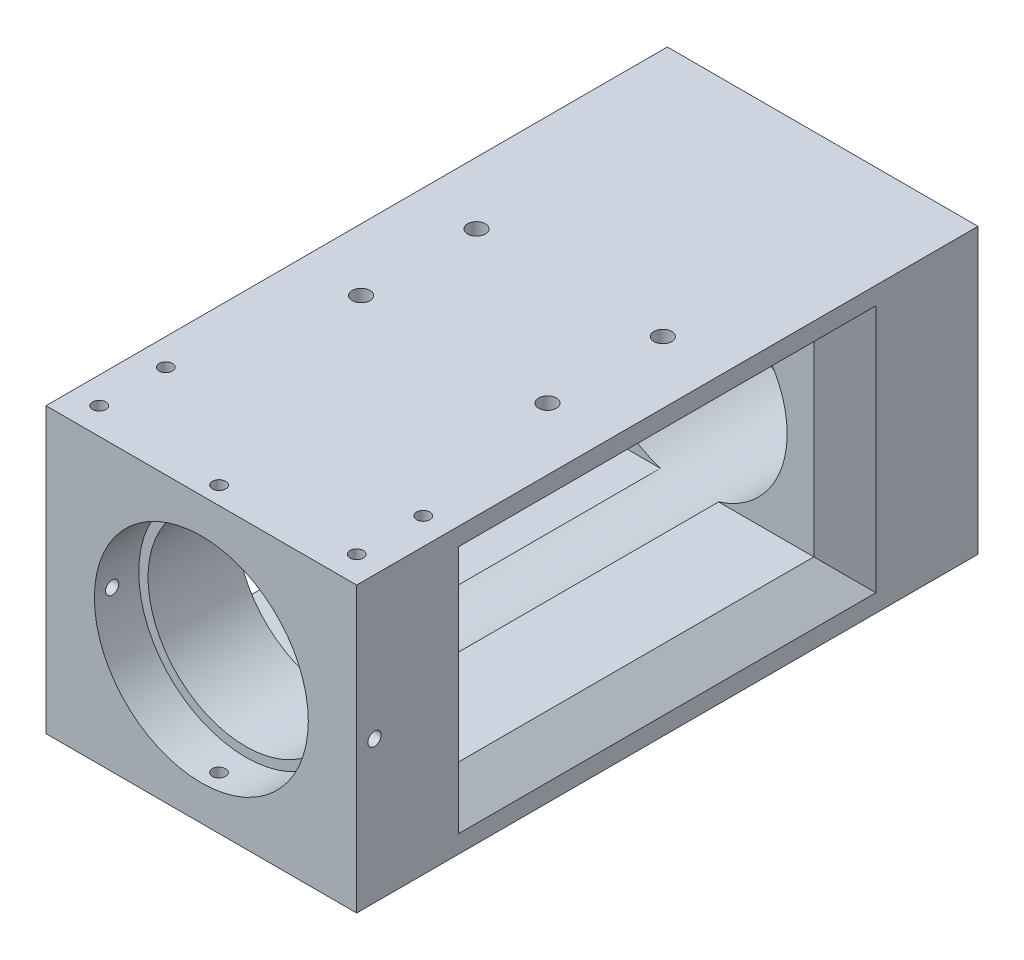
SolidWorks part; units mm, degrees
ref_plane "前视基准面" through (0, 0, 0) normal (0, 0, 1) x (1, 0, 0)
ref_plane "上视基准面" through (0, 0, 0) normal (0, 1, 0) x (1, 0, 0)
ref_plane "右视基准面" through (0, 0, 0) normal (1, 0, 0) x (0, 0, -1)
sketch "草图1" plane through (0, 0, 0) normal (0, 0, 1) x (1, 0, 0)
  line L1 (-35, -32) -> (35, -32)
  line L2 (-35, -32) -> (-35, 32)
  line L3 (-35, 32) -> (35, 32)
  line L4 (35, -32) -> (35, 32)
  line L5 (-35, -32) -> (35, 32) construction
  line L6 (-35, 32) -> (35, -32) construction
  point P0 (0, 0)
  dimension "D1" = 70
  dimension "D2" = 64
extrude "凸台-拉伸1" add sketch "草图1" along normal mid plane 140
sketch "草图2" plane through (0, 0, 70) normal (0, 0, 1) x (1, 0, 0)
  circle A0 centre (0, 0) radius 24.1
  dimension "D1" = 48.2
extrude "切除-拉伸1" cut sketch "草图2" against normal blind 10
sketch "草图3" plane through (0, 32, 0) normal (0, 1, 0) x (1, 0, 0)
  line L0 (35, -70) -> (-35, -70) construction
  circle A0 centre (0, -66) radius 1.5
  point P5 (0, -70)
  dimension "D1" = 3
  dimension "D2" = 4
extrude "切除-拉伸2" cut sketch "草图3" against normal through all
sketch "草图4" plane through (35, 0, 0) normal (1, 0, 0) x (0, 0, -1)
  line L0 (-70, -32) -> (-70, 32) construction
  circle A0 centre (-66, 0) radius 1.5
  dimension "D1" = 3
  dimension "D2" = 4
extrude "切除-拉伸3" cut sketch "草图4" against normal through all
sketch "草图5" plane through (0, 0, 60) normal (0, 0, 1) x (1, 0, 0)
  circle A0 centre (0, 0) radius 22
  dimension "D1" = 44
extrude "切除-拉伸4" cut sketch "草图5" against normal through all
sketch "草图6" plane through (35, 0, 0) normal (1, 0, 0) x (0, 0, -1)
  line L1 (-40, -21) -> (40, -21)
  line L2 (-40, -21) -> (-40, 21)
  line L3 (-40, 21) -> (40, 21)
  line L4 (40, -21) -> (40, 21)
  line L5 (-40, -21) -> (40, 21) construction
  line L6 (-40, 21) -> (40, -21) construction
  point P0 (0, 0)
  dimension "D1" = 42
  dimension "D2" = 80
extrude "切除-拉伸5" cut sketch "草图6" against normal through all
chamfer "倒角1" distance 7 angle 45 8 edges at (-35, 0, -40) (-35, -21, 0) (-35, 0, 40) (-35, 21, 0) (35, 21, 0) (35, 0, -40) (35, 0, 40) (35, -21, 0)
sketch "草图7" plane through (0, 32, 0) normal (0, 1, 0) x (1, 0, 0)
  line L0 (-21, 13) -> (21, 13) construction
  circle A0 centre (-21, 13) radius 2
  circle A1 centre (21, 13) radius 2
  point P4 (0, 13)
  dimension "D1" = 4
  dimension "D2" = 42
  dimension "D3" = 13
extrude "切除-拉伸6" cut sketch "草图7" against normal blind 20
sketch "草图8" plane through (0, 21, 0) normal (0, -1, 0) x (1, 0, 0)
  circle A1 centre (21, -13) radius 2 construction
  circle A2 centre (21, -13) radius 5.5
  circle A3 centre (21, -13) radius 5.5
  circle A4 centre (21, -13) radius 2
  circle M2 centre (21, -13) radius 2
  dimension "D1" = 3.5
extrude "切除-拉伸7" cut sketch "草图8" against normal blind 7 contours A3 M2 region at (15.6556, 21, -13)
mirror "镜向1" about plane through (0, 0, 0) normal (1, 0, 0) of "切除-拉伸7"
mirror "镜向2" about plane through (0, 0, 0) normal (0, 0, 1) of "镜向1", "切除-拉伸7", "切除-拉伸6"
sketch "草图9" plane through (0, 0, 0) normal (1, 0, 0) x (0, 0, -1)
  line L0 (-112.2479, 0) -> (108.0194, 0)
sketch "草图10" plane through (0, 0, -70) normal (0, 0, -1) x (-1, 0, 0)
  circle A0 centre (0, 0) radius 22 construction
  point P0 (0, -22)
sketch "草图11" plane through (0, 32, 0) normal (0, 1, 0) x (1, 0, 0)
  line L0 (-29, -64) -> (29, -64) construction
  line L1 (35, -70) -> (-35, -70) construction
  line L2 (-29, -49) -> (29, -49) construction
  circle A0 centre (-29, -64) radius 1.5
  circle A1 centre (29, -64) radius 1.5
  circle A2 centre (-29, -49) radius 1.5
  circle A3 centre (29, -49) radius 1.5
  point P4 (0, -64)
  point P7 (0, -70)
  point P12 (0, -49)
  dimension "D3" = 3
  dimension "D1" = 58
  dimension "D2" = 6
  dimension "D4" = 15
extrude "切除-拉伸8" cut sketch "草图11" against normal blind 10
